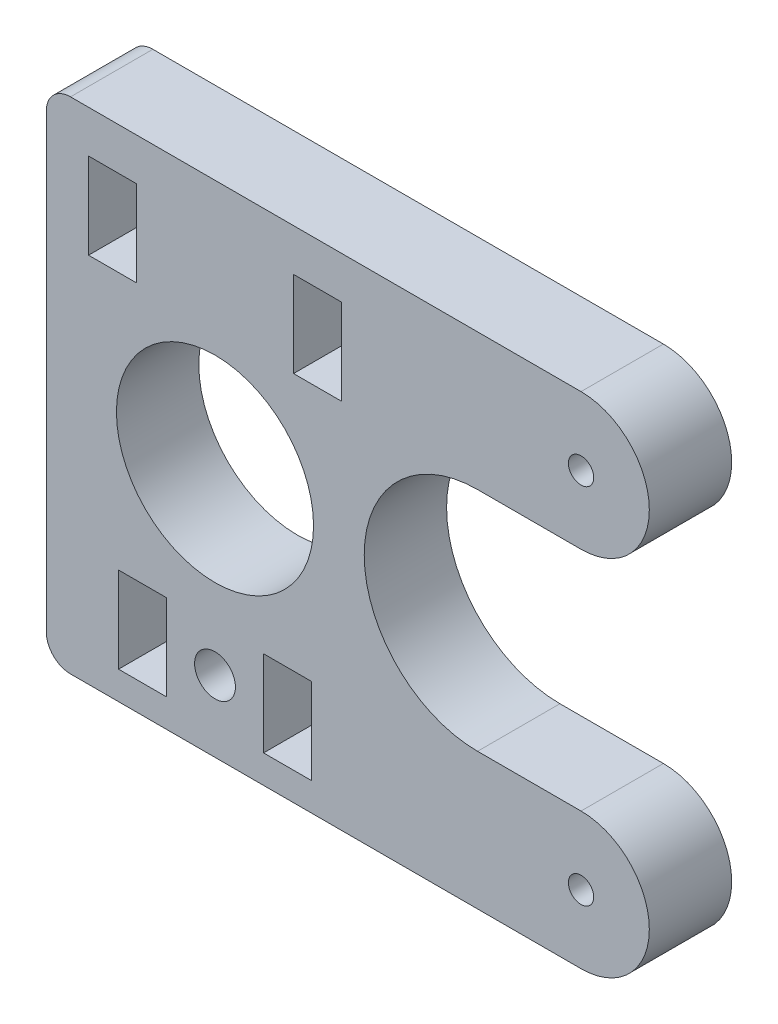
SolidWorks part; units mm, degrees
material "Acrylic (Medium-high impact)"
ref_plane "Front Plane" through (0, 0, 0) normal (0, 0, 1) x (1, 0, 0)
ref_plane "Top Plane" through (0, 0, 0) normal (0, 1, 0) x (1, 0, 0)
ref_plane "Right Plane" through (0, 0, 0) normal (1, 0, 0) x (0, 0, -1)
sketch "Sketch1" plane through (0, 0, 0) normal (0, 0, 1) x (1, 0, 0)
  line L0 (669.2168, 348.5155) -> (648.4638, 348.5155)
  line L1 (646.7465, 346.7982) -> (646.7465, 314.7328)
  line L2 (648.4638, 313.0155) -> (669.2168, 313.0155)
  line L3 (653.1465, 339.4155) -> (653.1465, 345.5155)
  line L4 (653.1465, 345.5155) -> (649.7465, 345.5155)
  line L5 (649.7465, 345.5155) -> (649.7465, 339.4155)
  line L6 (649.7465, 339.4155) -> (653.1465, 339.4155)
  line L7 (651.8765, 315.0155) -> (655.2765, 315.0155)
  line L8 (655.2765, 315.0155) -> (655.2765, 321.1155)
  line L9 (655.2765, 321.1155) -> (651.8765, 321.1155)
  line L10 (651.8765, 321.1155) -> (651.8765, 315.0155)
  line L11 (667.7065, 339.4155) -> (667.7065, 345.5155)
  line L12 (667.7065, 345.5155) -> (664.3065, 345.5155)
  line L13 (664.3065, 345.5155) -> (664.3065, 339.4155)
  line L14 (664.3065, 339.4155) -> (667.7065, 339.4155)
  line L15 (662.1765, 321.1155) -> (662.1765, 315.0155)
  line L16 (662.1765, 315.0155) -> (665.5765, 315.0155)
  line L17 (665.5765, 315.0155) -> (665.5765, 321.1155)
  line L18 (665.5765, 321.1155) -> (662.1765, 321.1155)
  line L19 (-318.4867, 330.7655) -> (49681.5133, 330.7655) construction
  line L21 (653.1465, 339.4155) -> (664.3065, 339.4155) construction
  line L22 (657.2765, 318.0655) -> (655.2765, 318.0655) construction
  line L23 (660.1765, 318.0655) -> (662.1765, 318.0655) construction
  line L24 (658.7265, -664.7806) -> (658.7265, 49335.2194) construction
  line L25 (669.2168, 313.0155) -> (684.7265, 313.0155)
  line L26 (669.2168, 348.5155) -> (684.7265, 348.5155)
  line L27 (684.7265, 317.8655) -> (684.7265, 330.7655) construction
  line L28 (684.7265, 330.7655) -> (684.7265, 343.6655) construction
  line L29 (684.7265, -669.3222) -> (684.7265, 49330.6778) construction
  line L30 (662.1765, 330.7655) -> (662.1765, 348.5155) construction
  line L31 (662.1765, 330.7655) -> (662.1765, 313.0155) construction
  line L32 (684.7265, 338.8155) -> (677.3765, 338.8155)
  line L33 (684.7265, 322.7155) -> (677.3765, 322.7155)
  circle A0 centre (684.7265, 343.6655) radius 0.9
  circle A1 centre (684.7265, 317.8655) radius 0.9
  arc A2 (684.7265, 313.0155) -> (684.7265, 322.7155) centre (684.7265, 317.8655) ccw
  circle A3 centre (658.7265, 318.0655) radius 1.45
  arc A4 (648.4638, 348.5155) -> (646.7465, 346.7982) centre (648.4638, 346.7982) ccw
  arc A5 (684.7265, 348.5155) -> (684.7265, 338.8155) centre (684.7265, 343.6655) cw
  arc A6 (677.3765, 338.8155) -> (677.3765, 322.7155) centre (677.3765, 330.7655) ccw
  arc A7 (646.7465, 314.7328) -> (648.4638, 313.0155) centre (648.4638, 314.7328) ccw
  circle A8 centre (658.7265, 330.7655) radius 7
  point P27 (658.7265, 339.4155)
  point P38 (669.3265, 330.7655)
  point P39 (665.7265, 330.7655)
  dimension "D5" = 2.9
  dimension "D12" = 3.6
  dimension "D13" = 14
  dimension "D14" = 1.8
  dimension "D15" = 1.7173
  dimension "D10" = 26
  dimension "D1" = 2
  dimension "D2" = 6.1
  dimension "D3" = 3.4
  dimension "D4" = 3.4
  dimension "D6" = 11.16
  dimension "D7" = 3
  dimension "D8" = 3
  dimension "D9" = 2
  dimension "D11" = 12.9
  dimension "D17" = 18.3
extrude "Boss-Extrude2" add sketch "Sketch1" along normal blind 5.85
